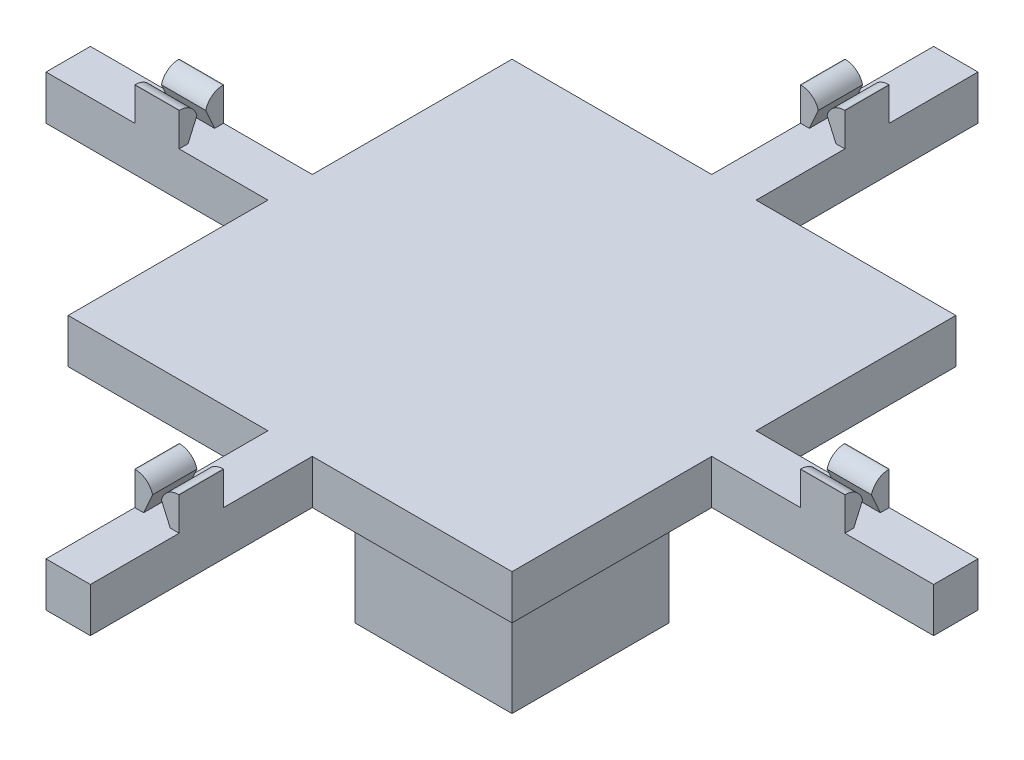
SolidWorks part; units mm, degrees
ref_plane "Front Plane" through (0, 0, 0) normal (0, 0, 1) x (1, 0, 0)
ref_plane "Top Plane" through (0, 0, 0) normal (0, 1, 0) x (1, 0, 0)
ref_plane "Right Plane" through (0, 0, 0) normal (1, 0, 0) x (0, 0, -1)
sketch "Sketch2" plane through (0, 0, 0) normal (0, 1, 0) x (1, 0, 0)
  line L1 (-50, -50) -> (50, -50)
  line L2 (-50, -50) -> (-50, 50)
  line L3 (-50, 50) -> (50, 50)
  line L4 (50, -50) -> (50, 50)
  line L5 (-50, -50) -> (50, 50) construction
  line L6 (-50, 50) -> (50, -50) construction
  point P0 (0, 0)
extrude "Boss-Extrude1" add sketch "Sketch2" along normal blind 5
sketch "Sketch3" plane through (0, 0, 0) normal (0, -1, 0) x (1, 0, 0)
  line L1 (-50, -50) -> (50, -50)
  line L2 (-50, -50) -> (-50, 50)
  line L3 (-50, 50) -> (50, 50)
  line L4 (50, -50) -> (50, 50)
  line L5 (-50, -50) -> (50, 50) construction
  line L6 (-50, 50) -> (50, -50) construction
  point P0 (0, 0)
extrude "Boss-Extrude2" add sketch "Sketch3" along normal blind 5
sketch "Sketch8" plane through (0, -5, 0) normal (0, -1, 0) x (1, 0, 0)
  circle A0 centre (0, 0) radius 5
extrude "Boss-Extrude7" add sketch "Sketch8" along normal blind 30
sketch "Sketch9" plane through (0, -35, 0) normal (0, -1, 0) x (1, 0, 0)
  line L1 (-17.7, 17.7) -> (17.7, 17.7)
  line L2 (-17.7, 17.7) -> (-17.7, -17.7)
  line L3 (-17.7, -17.7) -> (17.7, -17.7)
  line L4 (17.7, 17.7) -> (17.7, -17.7)
  line L5 (-17.7, 17.7) -> (17.7, -17.7) construction
  line L6 (-17.7, -17.7) -> (17.7, 17.7) construction
  point P0 (0, 0)
extrude "Boss-Extrude8" add sketch "Sketch9" along normal blind 20
sketch "Sketch10" plane through (0, -55, 0) normal (0, -1, 0) x (1, 0, 0)
  line L1 (-12.7, 12.7) -> (12.7, 12.7)
  line L2 (-12.7, 12.7) -> (-12.7, -12.7)
  line L3 (-12.7, -12.7) -> (12.7, -12.7)
  line L4 (12.7, 12.7) -> (12.7, -12.7)
  line L5 (-12.7, 12.7) -> (12.7, -12.7) construction
  line L6 (-12.7, -12.7) -> (12.7, 12.7) construction
  point P0 (0, 0)
extrude "Cut-Extrude1" cut sketch "Sketch10" against normal blind 12.7
sketch "Sketch11" plane through (50, 0, 0) normal (1, 0, 0) x (0, 0, -1)
  line L1 (-5, 5) -> (5, 5)
  line L2 (-5, 5) -> (-5, -5)
  line L3 (-5, -5) -> (5, -5)
  line L4 (5, 5) -> (5, -5)
  line L5 (-5, 5) -> (5, -5) construction
  line L6 (-5, -5) -> (5, 5) construction
  point P0 (0, 0)
extrude "Boss-Extrude9" add sketch "Sketch11" along normal blind 20
sketch "Sketch15" plane through (70, 0, 0) normal (1, 0, 0) x (0, 0, -1)
  line L0 (-5, -5) -> (5, -5)
  line L1 (5, -5) -> (5, 12.5)
  line L2 (-5, -5) -> (-5, 12.5)
  line L3 (-5, 12.5) -> (-1, 12.5)
  line L4 (5, 12.5) -> (1, 12.5)
  line L5 (-1, 12.5) -> (-1, 9.5)
  line L6 (1, 12.5) -> (1, 9.5)
  line L7 (5, 5) -> (-5, 5) construction
  line L8 (-3, 5) -> (3, 5)
  line L9 (3, 5) -> (1, 9.5)
  line L10 (-3, 5) -> (-1, 9.5)
  point P4 (3, 5)
  point P14 (-3, 5)
extrude "Boss-Extrude13" add sketch "Sketch15" along normal blind 10
fillet "Fillet3" radius 4 1 edges at (75, 12.5, 1)
fillet "Fillet5" radius 4 1 edges at (75, 12.5, -1)
sketch "Sketch16" plane through (80, 0, 0) normal (1, 0, 0) x (0, 0, -1)
  line L1 (-5, 5) -> (5, 5)
  line L2 (-5, 5) -> (-5, -5)
  line L3 (-5, -5) -> (5, -5)
  line L4 (5, 5) -> (5, -5)
  line L5 (-5, 5) -> (5, -5) construction
  line L6 (-5, -5) -> (5, 5) construction
  point P0 (0, 0)
extrude "Boss-Extrude14" add sketch "Sketch16" along normal blind 20
sketch "Sketch13" plane through (-50, 0, 0) normal (-1, 0, 0) x (0, 0, 1)
  line L0 (50, -5) -> (-50, -5) construction
  line L1 (-5, 5) -> (5, 5)
  line L2 (-5, 5) -> (-5, -5)
  line L3 (-5, -5) -> (5, -5)
  line L4 (5, 5) -> (5, -5)
  line L5 (-5, 5) -> (5, -5) construction
  line L6 (-5, -5) -> (5, 5) construction
  point P0 (0, 0)
extrude "Boss-Extrude11" add sketch "Sketch13" along normal blind 20
sketch "Sketch19" plane through (-70, 0, 0) normal (-1, 0, 0) x (0, 0, 1)
  line L0 (-5, -5) -> (5, -5)
  line L5 (3, 5) -> (-3, 5)
  line L6 (-5, -5) -> (-5, 12.4998)
  line L7 (-5, 5) -> (-5, 12.5) construction
  line L8 (-5, 12.4998) -> (-1, 12.4998)
  line L9 (-1, 12.4998) -> (-1, 9.5)
  line L10 (-1, 9.5) -> (-3, 5)
  line L11 (5, -5) -> (5, 12.5)
  line L12 (5, 12.5) -> (1, 12.5)
  line L13 (1, 12.5) -> (1, 9.5)
  line L14 (1, 9.5) -> (3, 5)
  point P10 (3, 5)
  point P11 (-3, 5)
extrude "Boss-Extrude17" add sketch "Sketch19" along normal blind 10
fillet "Fillet9" radius 4 1 edges at (-75, 12.4998, -1)
fillet "Fillet10" radius 4 1 edges at (-75, 12.5, 1)
sketch "Sketch21" plane through (-80, 0, 0) normal (-1, 0, 0) x (0, 0, 1)
  line L1 (-5, 5) -> (5, 5)
  line L2 (-5, 5) -> (-5, -5)
  line L3 (-5, -5) -> (5, -5)
  line L4 (5, 5) -> (5, -5)
  line L5 (-5, 5) -> (5, -5) construction
  line L6 (-5, -5) -> (5, 5) construction
  point P0 (0, 0)
extrude "Boss-Extrude18" add sketch "Sketch21" along normal blind 20
sketch "Sketch14" plane through (0, 0, -50) normal (0, 0, -1) x (-1, 0, 0)
  line L1 (-5, 5) -> (5, 5)
  line L2 (-5, 5) -> (-5, -5)
  line L3 (-5, -5) -> (5, -5)
  line L4 (5, 5) -> (5, -5)
  line L5 (-5, 5) -> (5, -5) construction
  line L6 (-5, -5) -> (5, 5) construction
  point P0 (0, 0)
extrude "Boss-Extrude12" add sketch "Sketch14" along normal blind 20
sketch "Sketch17" plane through (0, 0, -70) normal (0, 0, -1) x (-1, 0, 0)
  line L0 (-5, -5) -> (5, -5)
  line L1 (5, -5) -> (5, 12.5)
  line L2 (5, 12.5) -> (1, 12.5)
  line L3 (1, 12.5) -> (1, 9.5)
  line L4 (5, 5) -> (-5, 5) construction
  line L5 (1, 9.5) -> (3, 5)
  line L6 (3, 5) -> (-3, 5)
  line L7 (-5, -5) -> (-5, 12.5)
  line L8 (-5, 12.5) -> (-1, 12.5)
  line L9 (-1, 12.5) -> (-1, 9.5)
  line L10 (-1, 9.5) -> (-3, 5)
  point P4 (3, 5)
  point P8 (-3, 5)
  point P12 (1, 9.5)
extrude "Boss-Extrude15" add sketch "Sketch17" along normal blind 10
fillet "Fillet7" radius 4 1 edges at (1, 12.5, -75)
sketch "Sketch18" plane through (0, 0, -80) normal (0, 0, -1) x (-1, 0, 0)
  line L1 (-5, 5) -> (5, 5)
  line L2 (-5, 5) -> (-5, -5)
  line L3 (-5, -5) -> (5, -5)
  line L4 (5, 5) -> (5, -5)
  line L5 (-5, 5) -> (5, -5) construction
  line L6 (-5, -5) -> (5, 5) construction
  point P0 (0, 0)
extrude "Boss-Extrude16" add sketch "Sketch18" along normal blind 20
fillet "Fillet8" radius 4 1 edges at (-1, 12.5, -75)
sketch "Sketch12" plane through (0, 0, 50) normal (0, 0, 1) x (1, 0, 0)
  line L0 (50, -5) -> (-50, -5) construction
  line L1 (-5, 5) -> (5, 5)
  line L2 (-5, 5) -> (-5, -5)
  line L3 (-5, -5) -> (5, -5)
  line L4 (5, 5) -> (5, -5)
  line L5 (-5, 5) -> (5, -5) construction
  line L6 (-5, -5) -> (5, 5) construction
  line L7 (-5, -5) -> (5, -5) construction
  point P0 (0, 0)
extrude "Boss-Extrude10" add sketch "Sketch12" along normal blind 20
sketch "Sketch22" plane through (0, 0, 70) normal (0, 0, 1) x (1, 0, 0)
  line L0 (5, -5) -> (5, 12.5)
  line L1 (5, 12.5) -> (1, 12.5)
  line L2 (1, 12.5) -> (1, 9.5)
  line L3 (1, 9.5) -> (3, 5)
  line L4 (3, 5) -> (-3, 5)
  line L5 (-3, 5) -> (-1, 9.5)
  line L6 (-1, 9.5) -> (-1, 12.5)
  line L7 (-1, 12.5) -> (-5, 12.5)
  line L8 (5, -5) -> (-5, -5)
  line L9 (-5, -5) -> (-5, 12.5)
  point P4 (3, 5)
  point P7 (-3, 5)
extrude "Boss-Extrude19" add sketch "Sketch22" along normal blind 10
fillet "Fillet11" radius 4 1 edges at (-1, 12.5, 75)
fillet "Fillet12" radius 4 1 edges at (1, 12.5, 75)
sketch "Sketch23" plane through (0, 0, 80) normal (0, 0, 1) x (1, 0, 0)
  line L1 (-5, 5) -> (5, 5)
  line L2 (-5, 5) -> (-5, -5)
  line L3 (-5, -5) -> (5, -5)
  line L4 (5, 5) -> (5, -5)
  line L5 (-5, 5) -> (5, -5) construction
  line L6 (-5, -5) -> (5, 5) construction
  point P0 (0, 0)
extrude "Boss-Extrude20" add sketch "Sketch23" along normal blind 20
